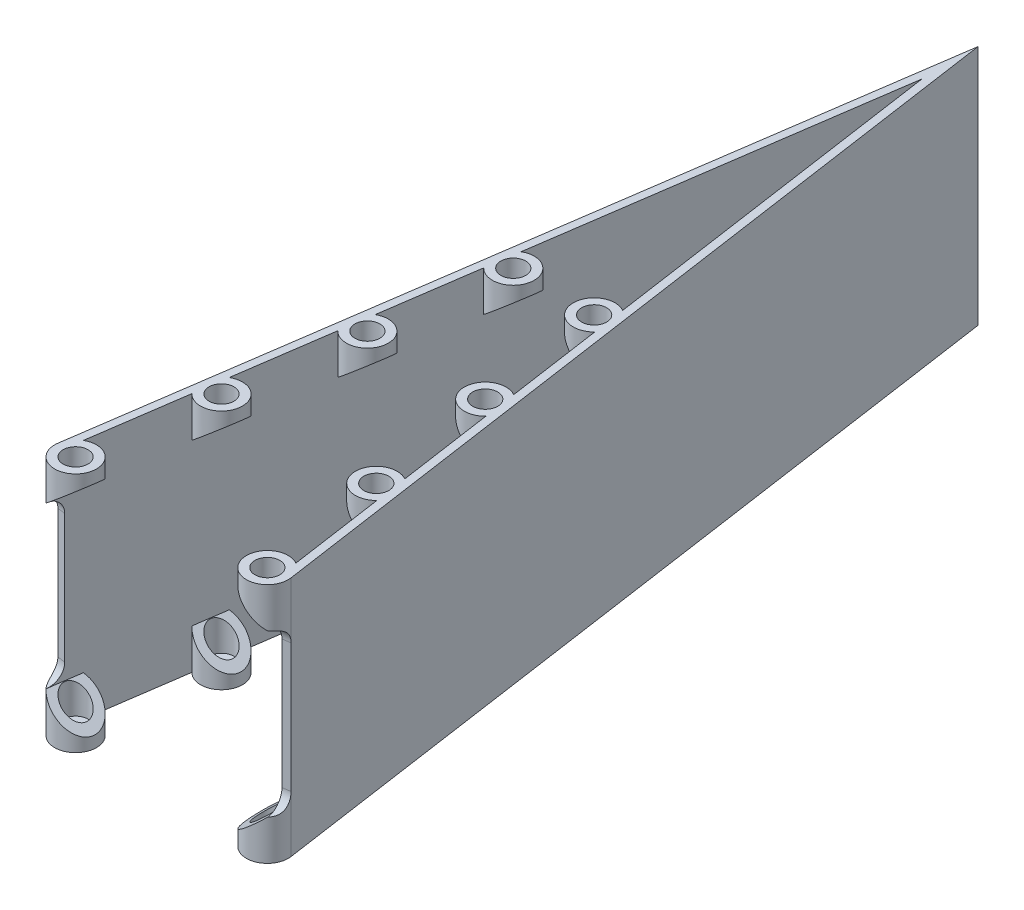
SolidWorks part; units mm, degrees
ref_plane "Front Plane" through (0, 0, 0) normal (0, 0, 1) x (1, 0, 0)
ref_plane "Top Plane" through (0, 0, 0) normal (0, 1, 0) x (1, 0, 0)
ref_plane "Right Plane" through (0, 0, 0) normal (1, 0, 0) x (0, 0, -1)
sketch "Sketch1" plane through (0, 0, 0) normal (0, 1, 0) x (1, 0, 0)
  line L0 (-13.5, 0) -> (13.5, 0) construction
  line L1 (-13.5, 0) -> (0, 93.0363)
  line L2 (0, 93.0363) -> (13.5, 0)
  line L3 (13.5, 0) -> (14.4896, 0.1436)
  line L4 (14.4896, 0.1436) -> (0, 100)
  line L5 (0, 100) -> (-14.4896, 0.1436)
  line L6 (-14.4896, 0.1436) -> (-13.5, 0)
  point P2 (0, 0)
  dimension "D1" = 90
  dimension "D2" = 90
  dimension "D4" = 1
  dimension "D5" = 27
  dimension "D3" = 100
extrude "Boss-Extrude1" add sketch "Sketch1" along normal blind 30
sketch "Sketch2" plane through (0, 0, 0) normal (0, 1, 0) x (1, 0, 0)
  line L0 (0, -1000) -> (0, 49000) construction
  line L1 (0, 93.0363) -> (13.5, 0) construction
  line L2 (0, 93.0363) -> (13.5, 0) construction
  line L3 (11.9166, -0.2298) -> (13.5, 0) construction
  line L4 (13.5, 0) -> (14.4896, 0.1436) construction
  line L5 (14.4896, 0.1436) -> (0, 100) construction
  line L6 (14.4896, 0.1436) -> (0, 100) construction
  circle A0 centre (11.9166, -0.2298) radius 2.6
  circle A1 centre (11.9166, -0.2298) radius 1.55
  circle A36 centre (9.619, 15.6044) radius 1.55
  circle A37 centre (9.619, 15.6044) radius 2.6
  circle A38 centre (7.3214, 31.4386) radius 1.55
  circle A39 centre (7.3214, 31.4386) radius 2.6
  circle A40 centre (5.0237, 47.2728) radius 1.55
  circle A41 centre (5.0237, 47.2728) radius 2.6
  circle A42 centre (-11.9166, -0.2298) radius 2.6
  circle A43 centre (-11.9166, -0.2298) radius 1.55
  circle A44 centre (-9.619, 15.6044) radius 2.6
  circle A45 centre (-9.619, 15.6044) radius 1.55
  circle A46 centre (-7.3214, 31.4386) radius 2.6
  circle A47 centre (-7.3214, 31.4386) radius 1.55
  circle A48 centre (-5.0237, 47.2728) radius 2.6
  circle A49 centre (-5.0237, 47.2728) radius 1.55
  dimension "D1" = 5.2
  dimension "D2" = 3.1
  dimension "D4" = 16
  dimension "D3" = 4
extrude "Boss-Extrude3" add sketch "Sketch2" along normal blind 5
sketch "Sketch4" plane through (0.2784, 0, 1.9185) normal (0.1436, 0, 0.9896) x (0.9896, 0, -0.1436)
  line L0 (9.1601, 5) -> (9.1601, 0) construction
  line L1 (14.3601, 5) -> (9.1601, 5) construction
  line L2 (13.3601, 30) -> (13.3601, 0) construction
  line L3 (9.1601, 5) -> (9.1601, 0) construction
  line L4 (14.3601, 5) -> (9.1601, 5) construction
  line L5 (13.3601, 30) -> (13.3601, 0) construction
  line L6 (13.3601, 5) -> (9.1601, 1.4758)
  line L7 (13.3601, 5) -> (9.1601, 5)
  line L8 (9.1601, 5) -> (9.1601, 1.4758)
  dimension "D1" = 40
extrude "Cut-Extrude1" cut sketch "Sketch4" against normal up to surface and the other way through all contours L7 L8 L6 up to face at (-8.9038, 5.5556, -31.6749)
sketch "Sketch5" plane through (-0.2784, 0, 1.9185) normal (-0.1436, 0, 0.9896) x (0.9896, 0, 0.1436)
  line L0 (-9.0831, 0) -> (-9.0831, 5) construction
  line L1 (-9.0831, 5) -> (-14.2831, 5) construction
  line L2 (-13.3601, 30) -> (-13.3601, 0) construction
  line L3 (-9.0831, 0) -> (-9.0831, 5) construction
  line L4 (-9.0831, 5) -> (-14.2831, 5) construction
  line L5 (-13.3601, 30) -> (-13.3601, 0) construction
  line L6 (-13.3601, 5) -> (-9.0831, 1.4112)
  line L7 (-13.3601, 5) -> (-9.0831, 5)
  line L8 (-9.0831, 5) -> (-9.0831, 1.4112)
  dimension "D1" = 40
extrude "Cut-Extrude2" cut sketch "Sketch5" against normal up to surface and the other way through all contours L8 L7 L6 up to face at (8.9038, 5.5556, -31.6749)
ref_plane "Plane1" through (0, 15, 0) normal (0, 1, 0) x (1, 0, 0)
mirror "Mirror2" about plane through (0, 15, 0) normal (0, 1, 0) of "Cut-Extrude2", "Cut-Extrude1", "Boss-Extrude3"
fillet "Fillet1" radius 2 4 edges at (13.9948, 5, -0.0718) (13.9948, 25, -0.0718) (-13.9948, 25, -0.0718) (-13.9948, 5, -0.0718)
sketch "Sketch6" plane through (0, 0, 0) normal (0, -1, 0) x (1, 0, 0)
  circle A0 centre (-9.619, -15.6044) radius 2.6
  arc A1 (14.4896, -0.1436) -> (13.2057, -2.0281) centre (11.9166, 0.2298) ccw construction
  circle A2 centre (9.619, -15.6044) radius 2.6
  circle A3 centre (7.3214, -31.4386) radius 2.6
  circle A4 centre (-7.3214, -31.4386) radius 2.6
  circle A5 centre (-5.0237, -47.2728) radius 2.6
  circle A6 centre (5.0237, -47.2728) radius 2.6
  arc A7 (-13.2057, -2.0281) -> (-14.4896, -0.1436) centre (-11.9166, 0.2298) ccw construction
  arc A8 (6.9015, -45.4744) -> (6.3129, -49.5307) centre (5.0237, -47.2728) ccw construction
  arc A9 (-6.3129, -49.5307) -> (-6.9015, -45.4744) centre (-5.0237, -47.2728) ccw construction
  arc A10 (-8.6105, -33.6965) -> (-9.1991, -29.6402) centre (-7.3214, -31.4386) ccw construction
  arc A11 (14.4896, -0.1436) -> (13.2057, -2.0281) centre (11.9166, 0.2298) ccw
  arc A12 (9.1991, -29.6402) -> (8.6105, -33.6965) centre (7.3214, -31.4386) ccw construction
  arc A13 (11.4967, -13.806) -> (10.9081, -17.8623) centre (9.619, -15.6044) ccw construction
  arc A14 (-10.9081, -17.8623) -> (-11.4967, -13.806) centre (-9.619, -15.6044) ccw construction
  arc A15 (-13.2057, -2.0281) -> (-14.4896, -0.1436) centre (-11.9166, 0.2298) ccw
  circle A16 centre (-11.9166, 0.2298) radius 2.6
  circle A28 centre (11.9166, 0.2298) radius 2.6
  arc A32 (6.9015, -45.4744) -> (6.3129, -49.5307) centre (5.0237, -47.2728) ccw
  arc A33 (-6.3129, -49.5307) -> (-6.9015, -45.4744) centre (-5.0237, -47.2728) ccw
  arc A34 (-8.6105, -33.6965) -> (-9.1991, -29.6402) centre (-7.3214, -31.4386) ccw
  arc A35 (9.1991, -29.6402) -> (8.6105, -33.6965) centre (7.3214, -31.4386) ccw
  arc A36 (11.4967, -13.806) -> (10.9081, -17.8623) centre (9.619, -15.6044) ccw
  arc A37 (-10.9081, -17.8623) -> (-11.4967, -13.806) centre (-9.619, -15.6044) ccw
extrude "Boss-Extrude4" add sketch "Sketch6" against normal blind 1
equation "\"D2@Sketch1\"=\"D1@Sketch1\""
